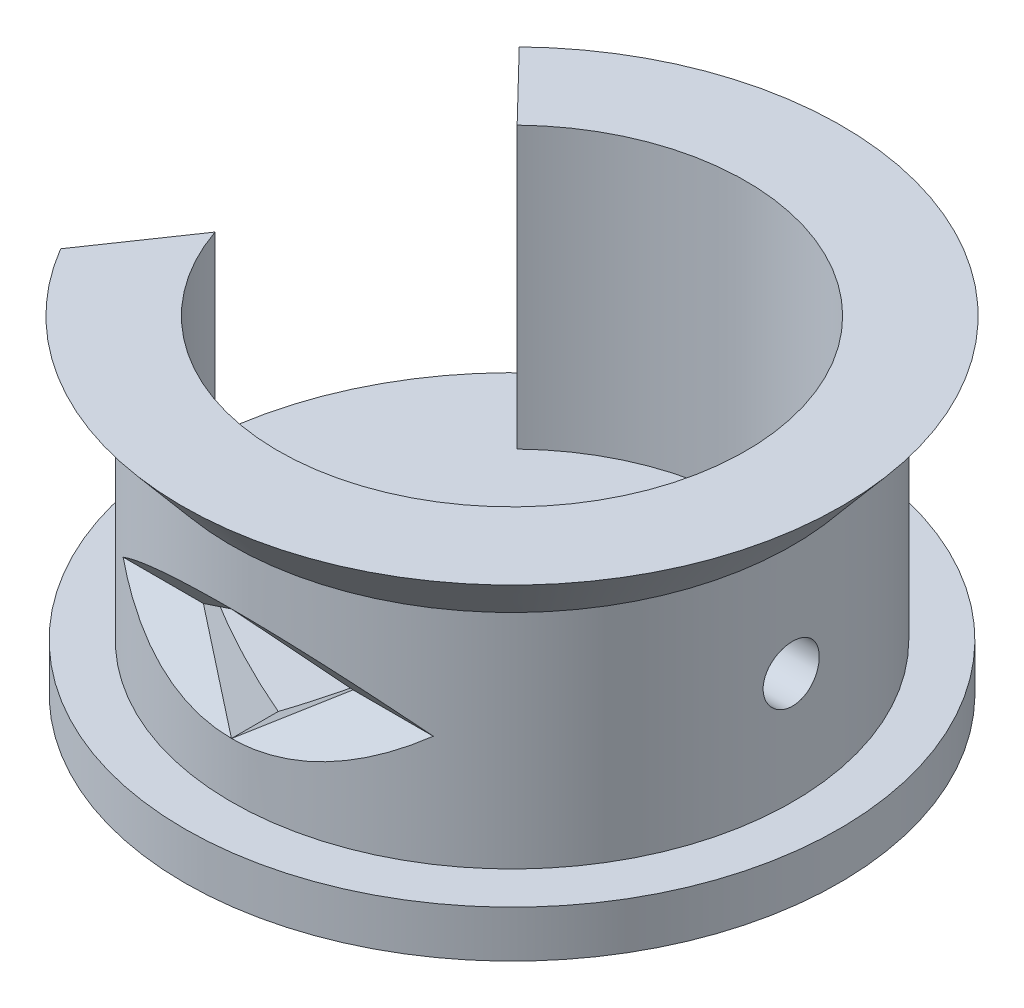
SolidWorks part; units mm, degrees
ref_plane "Front Plane" through (0, 0, 0) normal (0, 0, 1) x (1, 0, 0)
ref_plane "Top Plane" through (0, 0, 0) normal (0, 1, 0) x (1, 0, 0)
ref_plane "Right Plane" through (0, 0, 0) normal (1, 0, 0) x (0, 0, -1)
sketch "Sketch4" plane through (0, 0, 0) normal (0, 1, 0) x (1, 0, 0)
  circle A0 centre (0, 0) radius 7
extrude "Boss-Extrude3" add sketch "Sketch4" along normal blind 1
sketch "Sketch5" plane through (0, 1, 0) normal (0, 1, 0) x (1, 0, 0)
  circle A0 centre (0, 0) radius 6
  circle A1 centre (0, 0) radius 5
extrude "Boss-Extrude4" add sketch "Sketch5" along normal blind 4.75
sketch "Sketch6" plane through (0, 0, 0) normal (0, 0, 1) x (1, 0, 0)
  line L0 (0, 5.75) -> (6, 5.75)
  line L1 (5, 5.75) -> (-5, 5.75) construction
  line L7 (6, 7) -> (6, 5.75)
  line L8 (0, 7) -> (6, 7)
  line L10 (0, 5.75) -> (0, 7)
revolve "Revolve4" add sketch "Sketch6" angle 360 about L10
sketch "Sketch9" plane through (0, 7, 0) normal (0, 1, 0) x (1, 0, 0)
  circle A0 centre (0, 0) radius 5
extrude "Cut-Extrude3" cut sketch "Sketch9" against normal blind 3
sketch "Sketch11" plane through (0, 0, 0) normal (0, 0, 1) x (1, 0, 0)
  line L0 (0, 3.375) -> (0, 4.575)
  line L1 (0, 3.375) -> (0, 2.175)
  line L2 (0, 3.375) -> (-1.2, 3.375)
  line L3 (0, 3.375) -> (1.2, 3.375)
  line L5 (0, 2.175) -> (1.6, 3.375)
  line L6 (0, 4.575) -> (1.6, 3.375)
  line L7 (0, 3.375) -> (-1.6, 3.375)
  line L8 (-1.6, 3.375) -> (0, 4.575)
  line L9 (-1.6, 3.375) -> (0, 2.175)
  line L15 (0, 3.375) -> (1.6, 3.375)
extrude "Cut-Extrude7" cut sketch "Sketch11" along normal blind 10 contours L3 L15 L6 L0 | L8 L7 L2 L0 | L7 L9 L1 L2 | L15 L3 L1 L5 region at (-0.5333, 3.775, 0) region at (0.5333, 2.975, 0) region at (-0.5333, 2.975, 0) region at (0.5333, 3.775, 0)
sketch "Sketch12" plane through (0, 0, 0) normal (1, 0, 0) x (0, 0, -1)
  line L1 (6, 7) -> (-6, 7) construction
  line L5 (-6, 7) -> (-6, 5.75)
  line L6 (-6, 7) -> (-6, 4.575) construction
  line L7 (0, 7) -> (0, 8.25)
  line L8 (-7.0489, 7) -> (-6, 5.75)
  line L9 (-7.0489, 7) -> (-6, 7)
  line L10 (-7.0489, 7) -> (-6, 7)
revolve "Revolve8" add sketch "Sketch12" angle 360 about L7 region at (0, 6.5833, 6.3496)
sketch "Sketch13" plane through (0, 1, 0) normal (0, 1, 0) x (1, 0, 0)
  circle A0 centre (0, 0) radius 2.4
extrude "Cut-Extrude8" cut sketch "Sketch13" against normal blind 10
sketch "Sketch14" plane through (0, 7, 0) normal (0, 1, 0) x (1, 0, 0)
  line L0 (-4.73, -1.6207) -> (-6.071, -3.5819)
  line L1 (-3.4803, 3.5899) -> (-4.9065, 5.0609)
  circle A0 centre (0, 0) radius 5 construction
  circle A1 centre (0, 0) radius 7.0489 construction
  circle A2 centre (0, 0) radius 5 construction
  circle A3 centre (0, 0) radius 5
  circle A4 centre (0, 0) radius 7.0489
  circle M3 centre (0, 0) radius 5
  circle M4 centre (0, 0) radius 7.0489
extrude "Cut-Extrude9" cut sketch "Sketch14" against normal blind 6 contours L1 L0 M3 M4 region at (-5.6269, 7, -0.9729)
sketch "Sketch15" plane through (0, 0, 0) normal (1, 0, 0) x (0, 0, -1)
  line L0 (0, 1) -> (0, 5.75)
  line L1 (6, 1) -> (-6, 1) construction
  line L2 (-6, 5.75) -> (6, 5.75) construction
  circle A0 centre (0, 3.375) radius 0.6
extrude "Cut-Extrude10" cut sketch "Sketch15" along normal blind 10 contours L0 A0 | L0 A0 region at (0, 3.375, 0.2546) region at (0, 3.375, -0.2546)
sketch "Sketch16" plane through (0, 0, 0) normal (1, 0, 0) x (0, 0, -1)
  line L0 (-6, 4.575) -> (-5, 4.575)
  line L1 (-5, 4.575) -> (-5, 2.175)
  line L2 (-6, 2.175) -> (-5, 2.175)
  line L3 (-6, 4.575) -> (-6, 2.175)
  line L7 (-6, 4.575) -> (-5, 3.375)
  line L8 (-5, 3.375) -> (-6, 2.175)
extrude "Cut-Extrude14" cut sketch "Sketch16" against normal blind 10 and the other way blind 10 contours L8 L7 L3 region at (0, 3.375, 5.6667)
